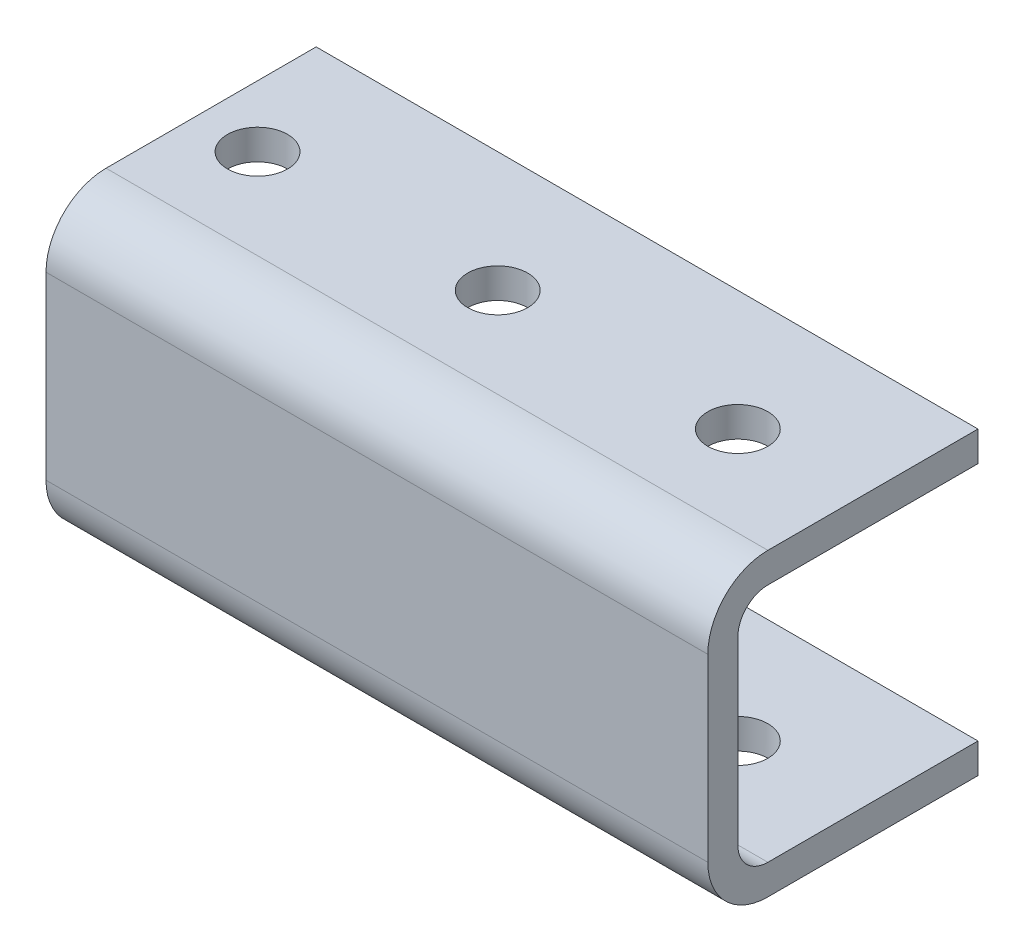
SolidWorks part; units mm, degrees
material "5052-O, Rod (SS)"
ref_plane "Front Plane" through (0, 0, 0) normal (0, 0, 1) x (1, 0, 0)
ref_plane "Top Plane" through (0, 0, 0) normal (0, 1, 0) x (1, 0, 0)
ref_plane "Right Plane" through (0, 0, 0) normal (1, 0, 0) x (0, 0, -1)
ref_plane "Plane1" through (0, 0, 3.175) normal (0, 0, 1) x (1, 0, 0)
sketch "Sketch1" plane through (0, 0, 3.175) normal (0, 0, 1) x (1, 0, 0)
  line L0 (872.98, -7.202) -> (872.98, 24.548)
  line L1 (872.98, 24.548) -> (-16.02, 24.548)
  line L2 (-16.02, 24.548) -> (-16.02, -7.202)
  line L3 (-16.02, -7.202) -> (872.98, -7.202)
extrude "Extrude1" add sketch "Sketch1" against normal blind 28.575
sketch "Sketch2" plane through (-16.02, 0, 0) normal (-1, 0, 0) x (0, 0, 1)
  line L0 (-25.4, 21.373) -> (-25.4, -4.027)
  line L1 (-25.4, -4.027) -> (0, -4.027)
  line L2 (0, -4.027) -> (0, 21.373)
  line L3 (0, 21.373) -> (-25.4, 21.373)
extrude "Extrude2" cut sketch "Sketch2" against normal up to next
hole_wizard "Hole1" positions "Sketch4" profile "Sketch3" legacy
sketch "Sketch4" plane through (0, 24.548, 0) normal (0, 1, 0) x (-1, 0, 0)
  point P0 (3.32, -12.7)
sketch "Sketch3" plane through (-3.32, 24.548, -12.7) normal (1, 0, 0) x (0, 0, 1)
  line L0 (0, 0) -> (0, 3.175)
  line L1 (0, 3.175) -> (3.175, 3.175)
  line L2 (3.175, 3.175) -> (3.175, 0)
  line L3 (3.175, 0) -> (0, 0)
  line L4 (0, 110) -> (0, -10) construction
  dimension "Diameter" = 6.35
  dimension "Depth" = 3.175
sketch3d "3DSketch1"
  point P0 (428.6664, 8.6668, -7.2024)
  point P1 (528.6664, 8.6668, -7.2024)
ref_axis "Axis1" through (528.6664, 8.6668, -7.2024) along (-1, 0, 0)
pattern_linear "LPattern1" count 35 spacing 25.4 along (1, 0, 0) of "Hole1"
hole_wizard "Hole2" positions "Sketch6" profile "Sketch5" legacy
sketch "Sketch6" plane through (0, 0, 3.175) normal (0, 0, 1) x (1, 0, 0)
  point P0 (66.53, 10.578)
sketch "Sketch5" plane through (66.53, 10.578, 3.175) normal (1, 0, 0) x (0, -1, 0)
  line L0 (0, 0) -> (0, 3.175)
  line L1 (0, 3.175) -> (4.826, 3.175)
  line L2 (4.826, 3.175) -> (4.826, 0)
  line L3 (4.826, 0) -> (0, 0)
  line L4 (0, 110) -> (0, -10) construction
  dimension "Diameter" = 9.652
  dimension "Depth" = 3.175
sketch3d "3DSketch2"
  point P0 (428.8468, 8.4517, -7.1294)
  point P1 (528.8468, 8.4517, -7.1294)
ref_axis "Axis2" through (528.8468, 8.4517, -7.1294) along (-1, 0, 0)
pattern_linear "LPattern2" count 12 spacing 25.4 along (1, 0, 0) skipping (2, 0), (3, 0), (4, 0), (5, 0), (6, 0), (7, 0), (8, 0), (9, 0) of "Hole2"
hole_wizard "Hole3" positions "Sketch8" profile "Sketch7" legacy
sketch "Sketch8" plane through (0, 0, 3.175) normal (0, 0, 1) x (1, 0, 0)
  point P0 (428.48, 6.768)
sketch "Sketch7" plane through (428.48, 6.768, 3.175) normal (1, 0, 0) x (0, -1, 0)
  line L0 (0, 0) -> (0, 3.175)
  line L1 (0, 3.175) -> (4.826, 3.175)
  line L2 (4.826, 3.175) -> (4.826, 0)
  line L3 (4.826, 0) -> (0, 0)
  line L4 (0, 110) -> (0, -10) construction
  dimension "Diameter" = 9.652
  dimension "Depth" = 3.175
hole_wizard "Hole4" positions "Sketch10" profile "Sketch9" legacy
sketch "Sketch10" plane through (0, 0, 3.175) normal (0, 0, 1) x (1, 0, 0)
  point P0 (511.03, 10.578)
sketch "Sketch9" plane through (511.03, 10.578, 3.175) normal (1, 0, 0) x (0, -1, 0)
  line L0 (0, 0) -> (0, 3.175)
  line L1 (0, 3.175) -> (4.826, 3.175)
  line L2 (4.826, 3.175) -> (4.826, 0)
  line L3 (4.826, 0) -> (0, 0)
  line L4 (0, 110) -> (0, -10) construction
  dimension "Diameter" = 9.652
  dimension "Depth" = 3.175
sketch3d "3DSketch3"
  point P0 (429.3014, 8.4448, -7.1738)
  point P1 (529.3014, 8.4448, -7.1738)
ref_axis "Axis3" through (529.3014, 8.4448, -7.1738) along (-1, 0, 0)
pattern_linear "LPattern3" count 12 spacing 25.4 along (1, 0, 0) skipping (2, 0), (3, 0), (4, 0), (5, 0), (6, 0), (7, 0), (8, 0), (9, 0) of "Hole4"
hole_wizard "Hole5" positions "Sketch12" profile "Sketch11" legacy
sketch "Sketch12" plane through (0, 0, 3.175) normal (0, 0, 1) x (1, 0, 0)
  point P0 (669.78, 8.673)
sketch "Sketch11" plane through (669.78, 8.673, 3.175) normal (1, 0, 0) x (0, -1, 0)
  line L0 (0, 0) -> (0, 3.175)
  line L1 (0, 3.175) -> (1.5875, 3.175)
  line L2 (1.5875, 3.175) -> (1.5875, 0)
  line L3 (1.5875, 0) -> (0, 0)
  line L4 (0, 110) -> (0, -10) construction
  dimension "Diameter" = 3.175
  dimension "Depth" = 3.175
hole_wizard "Hole6" positions "Sketch14" profile "Sketch13" legacy
sketch "Sketch14" plane through (0, -4.027, 0) normal (0, 1, 0) x (-1, 0, 0)
  point P0 (3.32, -12.7)
sketch "Sketch13" plane through (-3.32, -4.027, -12.7) normal (1, 0, 0) x (0, 0, 1)
  line L0 (0, 0) -> (0, 3.175)
  line L1 (0, 3.175) -> (3.175, 3.175)
  line L2 (3.175, 3.175) -> (3.175, 0)
  line L3 (3.175, 0) -> (0, 0)
  line L4 (0, 110) -> (0, -10) construction
  dimension "Diameter" = 6.35
  dimension "Depth" = 3.175
sketch3d "3DSketch4"
  point P0 (428.6444, 8.4444, -7.1991)
  point P1 (528.6444, 8.4444, -7.1991)
ref_axis "Axis4" through (528.6444, 8.4444, -7.1991) along (-1, 0, 0)
pattern_linear "LPattern4" count 35 spacing 25.4 along (1, 0, 0) of "Hole6"
fillet "Fillet1" radius 3.175 1 edges at (428.48, 21.373, 0) tangent propagation no
fillet "Fillet2" radius 3.175 1 edges at (428.48, -4.027, 0) tangent propagation no
fillet "Fillet3" radius 6.35 1 edges at (428.48, -7.202, 3.175) tangent propagation no
fillet "Fillet4" radius 6.35 1 edges at (428.48, 24.548, 3.175) tangent propagation no
ref_plane "Plane2" through (872.98, 24.548, -3.175) normal (1, 0, 0) x (0, 0, -1)
sketch "Sketch16" plane through (0, 24.548, 0) normal (0, 1, 0) x (1, 0, 0)
  line L0 (112.98, 3.175) -> (112.98, 25.4) construction
  line L1 (-16.02, 3.175) -> (872.98, 3.175) construction
  line L2 (872.98, 25.4) -> (-16.02, 25.4) construction
  line L3 (872.98, 25.4) -> (872.98, 3.175) construction
  line L6 (112.98, 3.175) -> (112.98, 25.4)
  line L7 (112.98, 25.4) -> (-16.02, 25.4)
  line L9 (112.98, 25.4) -> (-32.7801, 25.4)
  line L10 (112.98, 25.4) -> (112.98, -46.1048)
  line L11 (112.98, -46.1048) -> (-32.7801, -46.1048)
  line L12 (-32.7801, 25.4) -> (-32.7801, -46.1048)
  dimension "D1" = 760
extrude "Cut-Extrude2" cut sketch "Sketch16" against normal blind 75 contours L10 L11 L12 L9
sketch "Sketch17" plane through (0, 24.548, 0) normal (0, 1, 0) x (1, 0, 0)
  line L0 (524.98, 3.175) -> (524.98, 25.4) construction
  line L1 (112.98, 3.175) -> (872.98, 3.175) construction
  line L2 (872.98, 25.4) -> (112.98, 25.4) construction
  line L3 (872.98, 25.4) -> (872.98, 3.175) construction
  line L5 (524.98, 25.4) -> (51.3514, 25.4)
  line L6 (524.98, 25.4) -> (524.98, -41.5089)
  line L7 (524.98, -41.5089) -> (51.3514, -41.5089)
  line L8 (51.3514, 25.4) -> (51.3514, -41.5089)
  dimension "D1" = 348
extrude "Cut-Extrude3" cut sketch "Sketch17" against normal blind 186
sketch "Sketch18" plane through (0, 24.548, 0) normal (0, 1, 0) x (1, 0, 0)
  line L0 (802.98, 3.175) -> (802.98, 25.4) construction
  line L1 (524.98, 3.175) -> (872.98, 3.175) construction
  line L2 (872.98, 25.4) -> (524.98, 25.4) construction
  line L3 (872.98, 25.4) -> (872.98, 3.175) construction
  line L5 (802.98, 25.4) -> (429.8851, 25.4)
  line L6 (802.98, 25.4) -> (802.98, -68.5158)
  line L7 (802.98, -68.5158) -> (429.8851, -68.5158)
  line L8 (429.8851, 25.4) -> (429.8851, -68.5158)
  dimension "D1" = 70
extrude "Cut-Extrude4" cut sketch "Sketch18" against normal blind 186
